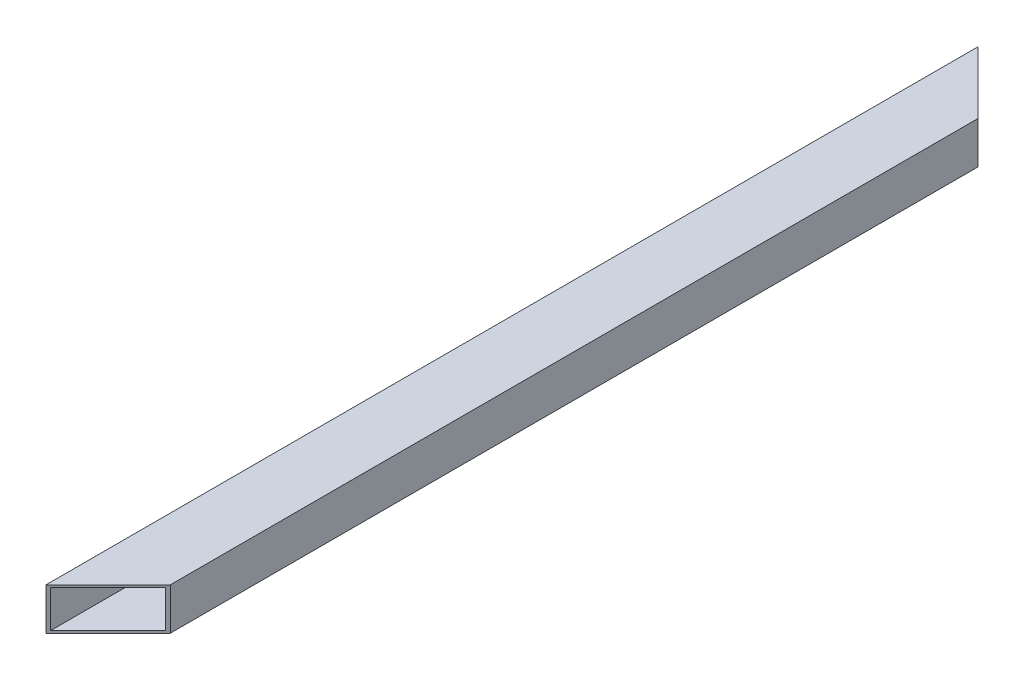
SolidWorks part; units mm, degrees
material "AISI 1045 Acier étiré à froid"
ref_plane "Plan de face" through (0, 0, 0) normal (0, 0, 1) x (1, 0, 0)
ref_plane "Plan de dessus" through (0, 0, 0) normal (0, 1, 0) x (1, 0, 0)
ref_plane "Plan de droite" through (0, 0, 0) normal (1, 0, 0) x (0, 0, -1)
sketch "Esquisse1" plane through (0, 0, 0) normal (0, 0, 1) x (1, 0, 0)
  line L1 (0, 0) -> (40, 0)
  line L2 (0, 0) -> (0, 27)
  line L3 (0, 27) -> (40, 27)
  line L4 (40, 0) -> (40, 27)
  line L5 (1.5, 25.5) -> (38.5, 25.5)
  line L6 (1.5, 25.5) -> (1.5, 1.5)
  line L7 (1.5, 1.5) -> (38.5, 1.5)
  line L8 (38.5, 25.5) -> (38.5, 1.5)
  dimension "D1" = 40
  dimension "D2" = 27
  dimension "D3" = 1.5
  dimension "D4" = 1.5
  dimension "D5" = 1.5
  dimension "D6" = 1.5
extrude "Boss.-Extru.1" add sketch "Esquisse1" along normal blind 600
sketch "Esquisse2" plane through (0, 0, 0) normal (0, 1, 0) x (1, 0, 0)
  line L0 (0, -600) -> (40, -560)
  line L1 (40, -600) -> (40, 0) construction
  line L2 (0, -600) -> (40, -600)
  line L3 (40, -600) -> (40, -560)
  dimension "D1" = 45
extrude "Enlèv. mat.-Extru.1" cut sketch "Esquisse2" along normal through all
sketch "Esquisse4" plane through (0, 0, 0) normal (0, 1, 0) x (1, 0, 0)
  line L0 (0, 0) -> (40, -40)
  line L1 (40, -560) -> (40, 0) construction
  line L2 (40, -40) -> (40, 0)
  line L3 (40, 0) -> (0, 0)
  dimension "D1" = 45
extrude "Enlèv. mat.-Extru.3" cut sketch "Esquisse4" along normal through all
